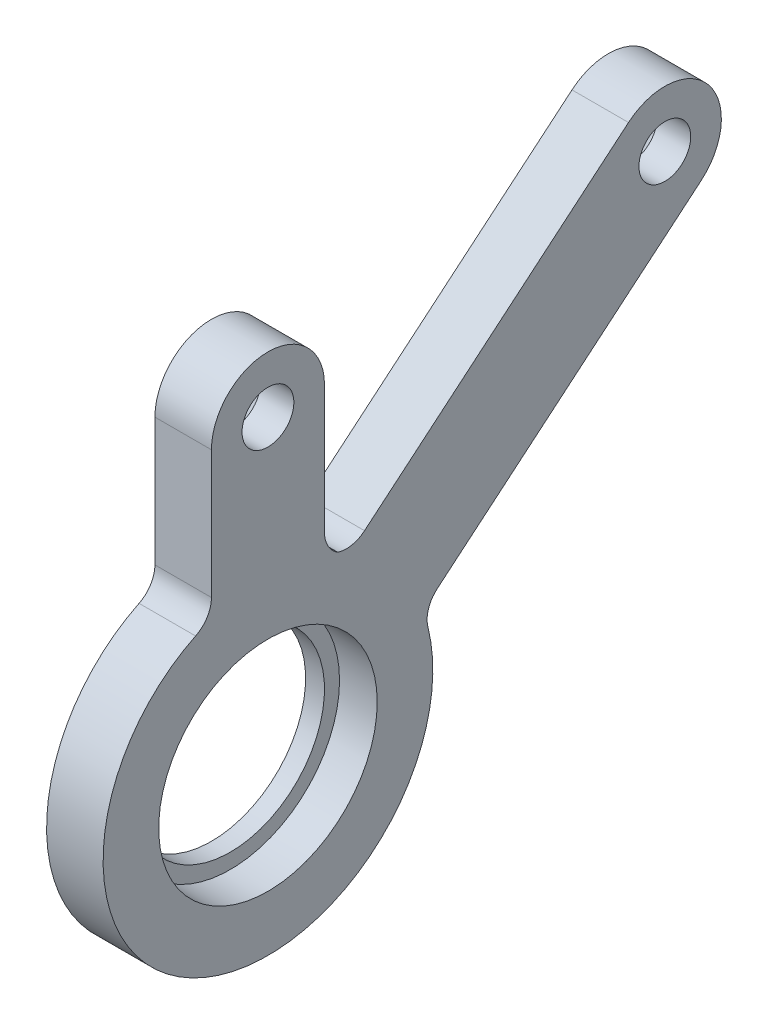
SolidWorks part; units mm, degrees
ref_plane "Front Plane" through (0, 0, 0) normal (0, 0, 1) x (1, 0, 0)
ref_plane "Top Plane" through (0, 0, 0) normal (0, 1, 0) x (1, 0, 0)
ref_plane "Right Plane" through (0, 0, 0) normal (1, 0, 0) x (0, 0, -1)
sketch "Sketch1" plane through (0, 0, 0) normal (1, 0, 0) x (0, 0, -1)
  circle A0 centre (0, 0) radius 11.6
  circle A1 centre (0, 0) radius 17.5
  dimension "D1" = 23.2
  dimension "D2" = 35
extrude "Boss-Extrude1" add sketch "Sketch1" along normal blind 4 and the other way blind 2
sketch "Sketch2" plane through (-2, 0, 0) normal (-1, 0, 0) x (0, 0, 1)
  line L4 (-38.2757, 39.9496) -> (-8.7365, 15.1632)
  line L5 (-45.9892, 30.7571) -> (-16.4499, 5.9707)
  line L6 (0, 0) -> (-42.1324, 35.3533) construction
  line L7 (-6, 32) -> (-6, 16.4393)
  line L8 (6, 32) -> (6, 16.4393)
  line L9 (0, 32) -> (0, 0) construction
  arc A0 (0, 17.5) -> (-6, 16.4393) centre (0, 0) ccw
  arc A2 (6, 32) -> (-6, 32) centre (0, 32) ccw
  circle A3 centre (0, 0) radius 17.5 construction
  arc A4 (6, 32) -> (-6, 32) centre (0, 32) ccw construction
  arc A8 (6, 16.4393) -> (0, 17.5) centre (0, 0) ccw
  arc A9 (6, 32) -> (-6, 32) centre (0, 32) ccw construction
  arc A10 (-38.2757, 39.9496) -> (-45.9892, 30.7571) centre (-42.1324, 35.3533) ccw
  arc A11 (-6, 16.4393) -> (-8.7365, 15.1632) centre (0, 0) ccw
  arc A12 (-6, 32) -> (0, 26) centre (0, 32) ccw construction
  arc A13 (-6, 32) -> (0, 26) centre (0, 32) ccw construction
  arc A14 (-6, 32) -> (0, 26) centre (0, 32) ccw construction
  arc A15 (0, 26) -> (6, 32) centre (0, 32) ccw construction
  arc A16 (0, 26) -> (6, 32) centre (0, 32) ccw construction
  arc A17 (0, 26) -> (6, 32) centre (0, 32) ccw construction
  arc A18 (-8.7365, 15.1632) -> (-13.4058, 11.2488) centre (0, 0) ccw
  arc A19 (-16.4499, 5.9707) -> (6, 16.4393) centre (0, 0) ccw
  arc A20 (-13.4058, 11.2488) -> (-16.4499, 5.9707) centre (0, 0) ccw
  arc A21 (-45.9892, 30.7571) -> (-37.5362, 31.4966) centre (-42.1324, 35.3533) ccw construction
  arc A22 (-37.5362, 31.4966) -> (-38.2757, 39.9496) centre (-42.1324, 35.3533) ccw construction
  circle M5 centre (0, 0) radius 17.5
  dimension "D1" = 12
  dimension "D3" = 55
  dimension "D4" = 12
  dimension "D5" = 50
  dimension "D2" = 32
extrude "Boss-Extrude2" add sketch "Sketch2" against normal up to surface (6 mm away) contours L4 A10 L5 M5 | L8 A2 L7 M5 region at (-2, 24.7162, -29.4556) region at (-2, 26.9749, 0) up to face at (4, 0, -17.5)
hole_wizard "CSK for M5 Countersunk Flat Head Screw2" positions "Sketch3" profile "Sketch4" countersink size "M5" standard "ISO" end condition up to next
sketch "Sketch3" plane through (-2, 0, 0) normal (-1, 0, 0) x (0, 0, 1)
  arc A2 (6, 32) -> (-6, 32) centre (0, 32) ccw construction
  arc A3 (6, 32) -> (-6, 32) centre (0, 32) ccw
  arc A4 (-38.2757, 39.9496) -> (-45.9892, 30.7571) centre (-42.1324, 35.3533) ccw construction
  arc A5 (-38.2757, 39.9496) -> (-45.9892, 30.7571) centre (-42.1324, 35.3533) ccw
  point P1 (0, 32)
  point P10 (-42.1324, 35.3533)
sketch "Sketch4" plane through (-2, 32, 0) normal (0, 1, 0) x (0, 0, 1)
  line L0 (0, 0) -> (0, 6)
  line L1 (0, 6) -> (2.75, 6)
  line L2 (2.75, 6) -> (2.75, 2.45)
  line L3 (2.75, 2.45) -> (5.2, 0)
  line L5 (5.2, 0) -> (0, 0)
  line L6 (-2.75, 2.45) -> (-5.2, 0) construction
  line L11 (0, -6.35) -> (0, 107.95) construction
  dimension "Thru Hole Dia." = 5.5
  dimension "Thru Hole Depth" = 6
  dimension "Near C'Sink Dia." = 10.4
  dimension "Near C'Sink Angle" = 90
fillet "Fillet1" radius 3 4 edges at (1, 16.4393, 6) (1, 5.9707, -16.4499) (1, 15.1632, -8.7365) (1, 16.4393, -6)
sketch "Sketch5" plane through (-2, 0, 0) normal (-1, 0, 0) x (0, 0, 1)
  circle A0 centre (0, 0) radius 10
  circle A1 centre (0, 0) radius 11.6 construction
  circle A2 centre (0, 0) radius 11.6
  dimension "D1" = 20
extrude "Boss-Extrude3" add sketch "Sketch5" against normal blind 2
